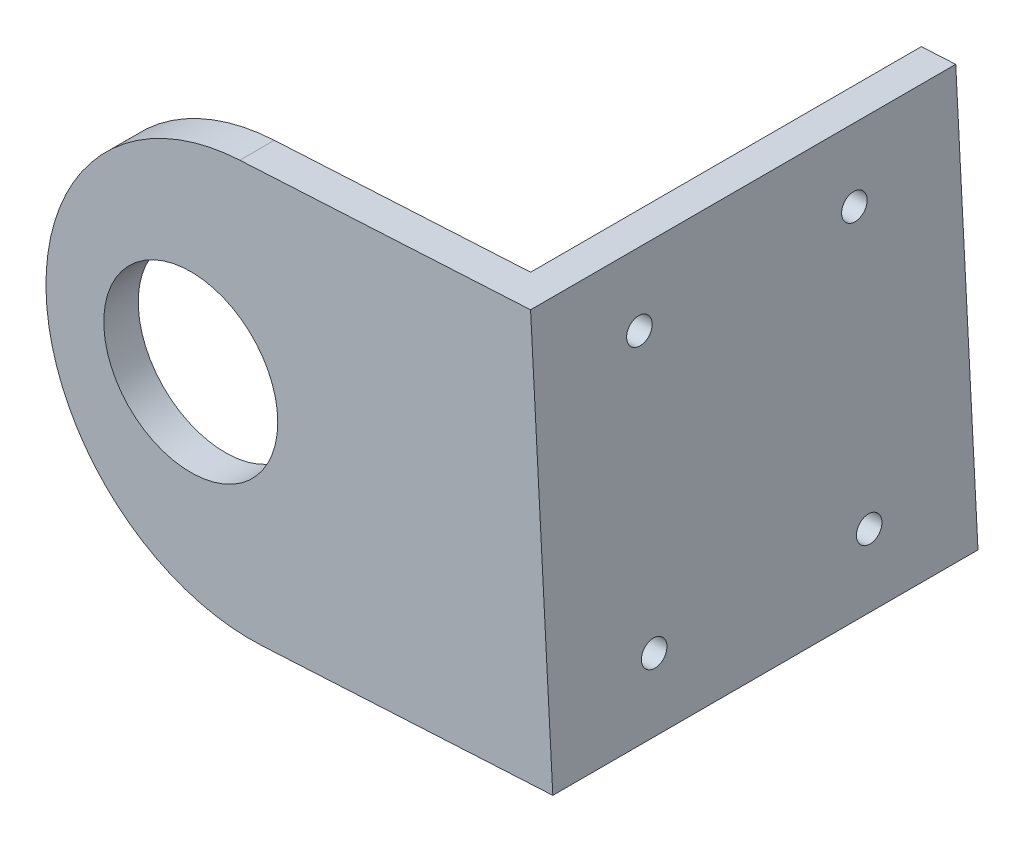
SolidWorks part; units mm, degrees
ref_plane "Front Plane" through (0, 0, 0) normal (0, 0, 1) x (1, 0, 0)
ref_plane "Top Plane" through (0, 0, 0) normal (0, 1, 0) x (1, 0, 0)
ref_plane "Right Plane" through (0, 0, 0) normal (1, 0, 0) x (0, 0, -1)
sketch "Sketch1" plane through (0, 0, 0) normal (0, 0, 1) x (1, 0, 0)
  line L0 (44.3166, 32.2041) -> (47.5477, -27.2081) construction
  line L4 (-22.5845, 28.5657) -> (44.3166, 32.2041)
  line L5 (44.3166, 32.2041) -> (47.5477, -27.2081)
  line L6 (47.5477, -27.2081) -> (-19.3535, -30.8465)
  line L7 (-19.3535, -30.8465) -> (-22.5845, 28.5657)
  line L8 (7.1216, 30.1813) -> (39.324, 31.9326) construction
  line L9 (42.555, -27.4797) -> (10.3526, -29.2309) construction
  arc A0 (7.1216, 30.1813) -> (10.3526, -29.2309) centre (8.7371, 0.4752) ccw construction
  circle A1 centre (0, 0) radius 12.375 construction
  circle A2 centre (0, 0) radius 12.625
  circle A3 centre (0, 0) radius 12.375 construction
  point P18 (0, 0)
  dimension "D1" = 0.25
extrude "Boss-Extrude1" add sketch "Sketch1" along normal blind 5
sketch "Sketch2" plane through (45.9321, 2.498, 0) normal (0.9985, 0.0543, 0) x (0, 0, -1)
  line L0 (-5, 29.75) -> (56.7, 29.75)
  line L1 (56.7, 29.75) -> (56.7, -29.75)
  line L2 (56.7, -29.75) -> (-5, -29.75)
  line L3 (-5, -29.75) -> (-5, 29.75)
  circle A0 centre (10.25, 19.75) radius 1.85 construction
  circle A1 centre (41.45, 19.75) radius 1.85 construction
  circle A2 centre (41.45, -19.75) radius 1.85 construction
  circle A3 centre (10.25, -19.75) radius 1.85 construction
  circle A4 centre (10.25, 19.75) radius 1.85
  circle A5 centre (41.45, 19.75) radius 1.85
  circle A6 centre (41.45, -19.75) radius 1.85
  circle A7 centre (10.25, -19.75) radius 1.85
extrude "Boss-Extrude2" add sketch "Sketch2" along normal blind 5
fillet "Fillet1" 2 edges at (-22.5845, 28.5657, 2.5) (-19.3535, -30.8465, 2.5) type full round first side face at (29.2555, 31.385, -21.9583) second side face at (21.3364, -28.6336, -12.5083) middle face at (-20.969, -1.1404, 2.5)
